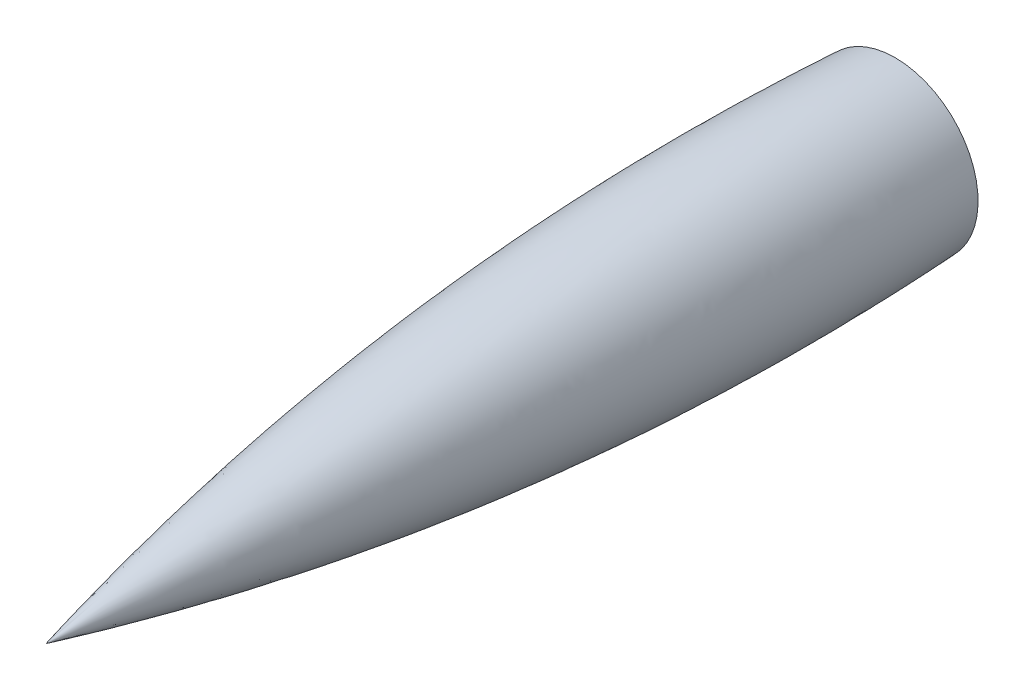
SolidWorks part; units mm, degrees
ref_plane "Front Plane" through (0, 0, 0) normal (0, 0, 1) x (1, 0, 0)
ref_plane "Top Plane" through (0, 0, 0) normal (0, 1, 0) x (1, 0, 0)
ref_plane "Right Plane" through (0, 0, 0) normal (1, 0, 0) x (0, 0, -1)
sketch "Sketch1" plane through (0, 0, 0) normal (1, 0, 0) x (0, 0, -1)
  line L0 (0, 50.8) -> (0, 0)
  line L1 (0, 0) -> (-520.7308, 0)
  spline S0 degree 4 poles (-571.0294, -13.4763) (-570.2418, -13.2527) (-568.6665, -12.8066) (-565.5158, -11.9184) (-560.7839, -10.5973) (-555.2626, -9.0742) (-549.7391, -7.5728) (-545.02, -6.3056) (-541.0842, -5.2594) (-537.9751, -4.4387) (-534.8037, -3.6085) (-531.7618, -2.8171) (-528.439, -1.961) (-525.7179, -1.2628) (-521.7347, -0.2526) (-519.8086, 0.233) (-515.9343, 1.2038) (-513.255, 1.8677) (-510.0675, 2.654) (-507.0979, 3.3796) (-504.0303, 4.1242) (-501.0039, 4.8526) (-497.1979, 5.7617) (-492.6375, 6.8395) (-485.7862, 8.4374) (-478.1683, 10.1758) (-470.5403, 11.8784) (-462.9055, 13.5446) (-456.7924, 14.8558) (-449.1456, 16.4676) (-439.9601, 18.3581) (-429.2309, 20.4999) (-416.9517, 22.8603) (-404.6561, 25.1331) (-386.1887, 28.4108) (-352.262, 34.0174) (-308.9191, 40.1261) (-262.2986, 45.2339) (-221.7898, 48.5066) (-196.8328, 50.1056) (-181.2261, 50.9567) (-168.7361, 51.5486) (-156.2423, 52.0514) (-143.7451, 52.4652) (-131.2454, 52.7898) (-118.7436, 53.0254) (-107.8035, 53.1535) (-98.4256, 53.2076) (-90.6109, 53.2156) (-84.3586, 53.1997) (-76.5447, 53.152) (-68.7285, 53.067) (-60.9172, 52.9452) (-53.1001, 52.7858) (-46.8564, 52.6366) (-40.5947, 52.4641) (-35.1476, 52.2953) (-30.4293, 52.1341) (-25.7976, 51.9663) (-21.0006, 51.7786) (-15.7554, 51.5619) (-9.9383, 51.2956) (-5.7848, 51.0971) (-1.0488, 50.8554) (0.9041, 50.753) (4.6169, 50.5531) (7.2979, 50.4024) (10.3379, 50.228) (13.2494, 50.0553) (16.2085, 49.8751) (19.1483, 49.6909) (22.0956, 49.5014) (25.0394, 49.3072) (28.7202, 49.058) (33.1358, 48.7492) (37.5509, 48.428) (41.9649, 48.0944) (44.9071, 47.8654) (46.3781, 47.7492) (47.1135, 47.6908) knots 0 0 0 0 0 0.005243 0.010487 0.020974 0.03146 0.041947 0.047128 0.052308 0.057489 0.06267 0.06785 0.073031 0.078211 0.083392 0.088398 0.093404 0.09841 0.103416 0.108422 0.113428 0.118433 0.123439 0.133451 0.143463 0.163487 0.173499 0.18351 0.193522 0.203534 0.223558 0.243581 0.263605 0.283629 0.303652 0.363723 0.483865 0.56396 0.604007 0.624031 0.644055 0.664078 0.684102 0.704126 0.724149 0.744173 0.764197 0.774209 0.78422 0.794232 0.804244 0.824268 0.83428 0.844291 0.854303 0.864315 0.874327 0.879333 0.884339 0.89435 0.904362 0.914374 0.91938 0.924386 0.929112 0.933838 0.938564 0.943289 0.948015 0.952741 0.957467 0.962193 0.966919 0.971645 0.981096 0.990548 0.995274 1 1 1 1 1 construction
  spline S1 degree 4 poles (-520.7308, 0) (-520.0935, 0.1606) (-518.8149, 0.482) (-515.9343, 1.2038) (-513.255, 1.8677) (-510.0675, 2.654) (-507.0979, 3.3796) (-504.0303, 4.1242) (-501.0039, 4.8526) (-497.1979, 5.7617) (-492.6375, 6.8395) (-485.7862, 8.4374) (-478.1683, 10.1758) (-470.5403, 11.8784) (-462.9055, 13.5446) (-456.7924, 14.8558) (-449.1456, 16.4676) (-439.9601, 18.3581) (-429.2309, 20.4999) (-416.9517, 22.8603) (-404.6561, 25.1331) (-386.1887, 28.4108) (-352.262, 34.0174) (-308.9191, 40.1261) (-262.2986, 45.2339) (-221.7898, 48.5066) (-196.8328, 50.1056) (-181.2261, 50.9567) (-168.7361, 51.5486) (-156.2423, 52.0514) (-143.7451, 52.4652) (-131.2454, 52.7898) (-118.7436, 53.0254) (-107.8035, 53.1535) (-98.4256, 53.2076) (-90.6109, 53.2156) (-84.3586, 53.1997) (-76.5447, 53.152) (-68.7285, 53.067) (-60.9172, 52.9452) (-53.1001, 52.7858) (-46.8564, 52.6366) (-40.5947, 52.4641) (-35.1476, 52.2953) (-30.4293, 52.1341) (-25.7976, 51.9663) (-21.0006, 51.7786) (-15.7554, 51.5619) (-9.9383, 51.2956) (-5.7848, 51.0971) (-1.9531, 50.9016) (-0.6563, 50.8344) (0, 50.8) knots 0.083392 0.083392 0.083392 0.083392 0.083392 0.088398 0.093404 0.09841 0.103416 0.108422 0.113428 0.118433 0.123439 0.133451 0.143463 0.163487 0.173499 0.18351 0.193522 0.203534 0.223558 0.243581 0.263605 0.283629 0.303652 0.363723 0.483865 0.56396 0.604007 0.624031 0.644055 0.664078 0.684102 0.704126 0.724149 0.744173 0.764197 0.774209 0.78422 0.794232 0.804244 0.824268 0.83428 0.844291 0.854303 0.864315 0.874327 0.879333 0.884339 0.89435 0.904362 0.914374 0.91938 0.924386 0.924386 0.924386 0.924386 0.924386
  point P0 (0, 429.0136)
  dimension "D1" = 50.8
revolve "Revolve1" add sketch "Sketch1" angle 360 about L1
equation "\"R\" = 2'base radius"
equation "\"L\"= 16.5'overall length"
equation "\"rho\"= ( \"R\" ^ 2 + \"L\" ^ 2 ) / ( 2 * \"R\" )'ogive radius"
equation "\"alpha\"= arccos ( sqr ( \"L\" ^ 2 + \"R\" ^ 2 ) / ( 2 * \"rho\" ) ) - atn ( \"R\" / \"L\" )"
